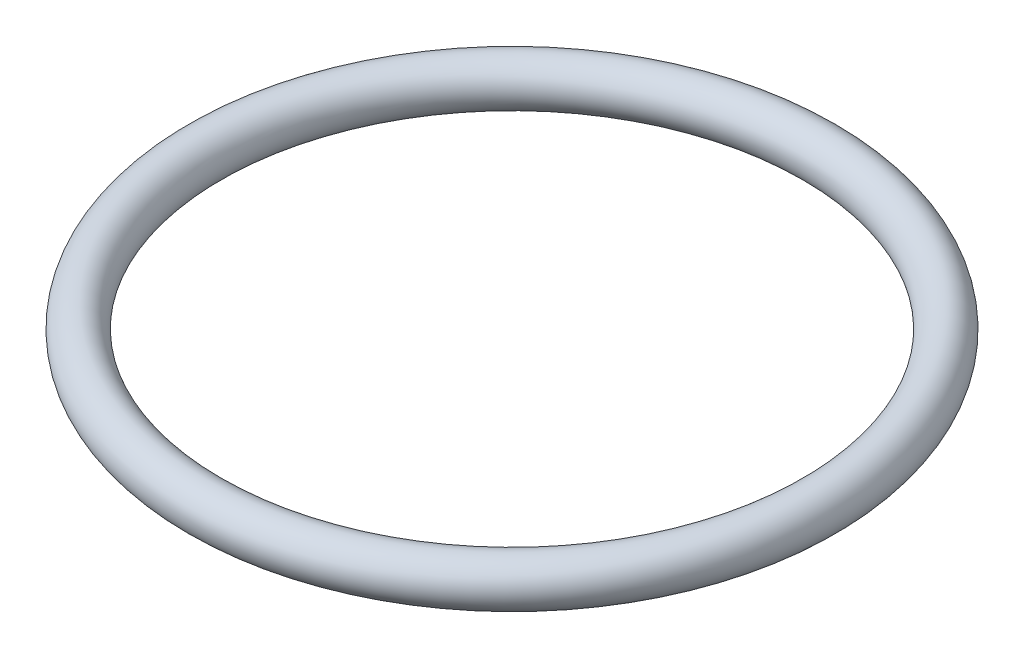
SolidWorks part; units mm, degrees
ref_plane "Front Plane" through (0, 0, 0) normal (0, 0, 1) x (1, 0, 0)
ref_plane "Top Plane" through (0, 0, 0) normal (0, 1, 0) x (1, 0, 0)
ref_plane "Right Plane" through (0, 0, 0) normal (1, 0, 0) x (0, 0, -1)
sketch "Sketch1" plane through (0, 0, 0) normal (0, 1, 0) x (1, 0, 0)
  circle A1 centre (0, 0) radius 22.0218
  dimension "B" = 44.0436
sketch "Sketch2" plane through (0, 0, 0) normal (0, 0, 1) x (1, 0, 0)
  circle A0 centre (-23.7871, 0) radius 1.7653
  point P4 (-22.0218, 0)
  dimension "A" = 3.5306
sweep "Sweep1" add profiles "Sketch2" path "Sketch1"
ref_axis "Axis1" through (0, 5.2562, 0) along (0, -1, 0)
